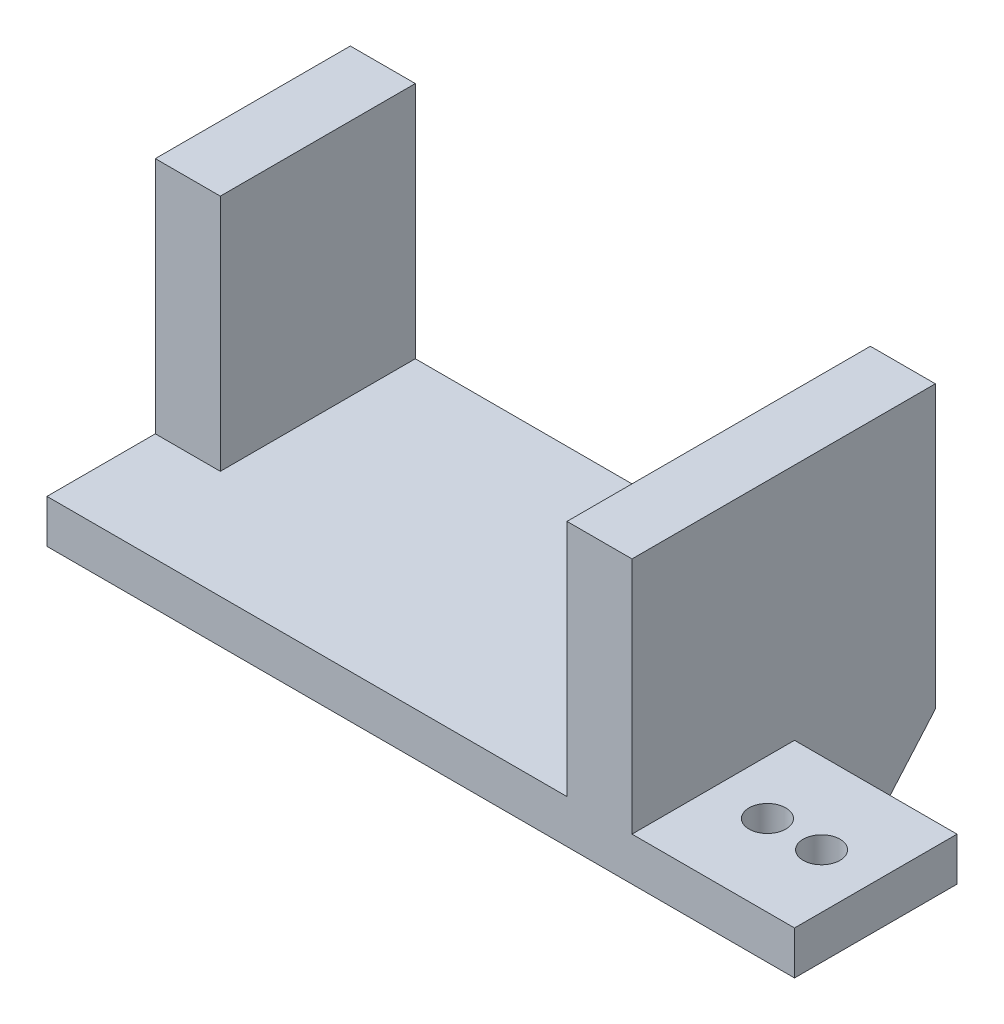
SolidWorks part; units mm, degrees
ref_plane "Front" through (0, 0, 0) normal (0, 0, 1) x (1, 0, 0)
ref_plane "Top" through (0, 0, 0) normal (0, 1, 0) x (1, 0, 0)
ref_plane "Right" through (0, 0, 0) normal (1, 0, 0) x (0, 0, -1)
sketch "Sketch1" plane through (0, 0, 0) normal (0, 0, 1) x (1, 0, 0)
  line L0 (-21, 0) -> (21, 0)
  line L1 (21, 0) -> (21, 26)
  line L2 (21, 26) -> (27, 26)
  line L3 (27, 26) -> (27, 4)
  line L4 (27, 4) -> (42, 4)
  line L5 (42, 4) -> (42, 0)
  line L6 (42, 0) -> (21, 0)
  line L7 (21, 4) -> (-21, 4)
  line L8 (0, 4) -> (0, 0)
  line L9 (-42, 0) -> (-21, 0)
  line L10 (-42, 4) -> (-42, 0)
  line L11 (-27, 4) -> (-42, 4)
  line L12 (-27, 26) -> (-27, 4)
  line L13 (-21, 26) -> (-27, 26)
  line L14 (-21, 0) -> (-21, 26)
  point P4 (0, 0)
  point P19 (24, 26)
  point P20 (-24, 26)
  dimension "D1" = 4
  dimension "D2" = 6
  dimension "D3" = 26
  dimension "D4" = 15
  dimension "D5" = 48
  dimension "D6" = 0
extrude "Boss-Extrude1" add sketch "Sketch1" along normal blind 15 contours L6 L5 L4 L3 L2 L1 | L14 L0 L8 L7 | L7 L8 L0 L1 | L9 L14 L13 L12 L11 L10 region at (-10.5, 2, 0) region at (-26.9167, 9.9444, 0) region at (10.5, 2, 0) region at (26.9167, 9.9444, 0)
sketch "Sketch2" plane through (0, 0, 0) normal (0, 0, -1) x (-1, 0, 0)
  line L0 (-27, 26) -> (-27, 0)
  line L1 (-42, 0) -> (42, 0) construction
  line L2 (-27, 26) -> (-21, 26)
  line L3 (-21, 26) -> (-27, 26) construction
  line L4 (-21, 26) -> (-21, 4)
  line L5 (-21, 4) -> (21, 4)
  line L6 (21, 4) -> (21, 26)
  line L7 (21, 26) -> (27, 26)
  line L8 (27, 26) -> (27, 4)
  line L9 (27, 4) -> (27, 0)
  line L10 (27, 0) -> (-27, 0)
extrude "Boss-Extrude2" add sketch "Sketch2" along normal blind 13
sketch "Sketch3" plane through (0, 0, -13) normal (0, 0, -1) x (-1, 0, 0)
  line L0 (-24, 26) -> (-24, 6)
  line L2 (-21, 26) -> (-27, 26) construction
  line L3 (24, 26) -> (24, 6)
  line L5 (27, 26) -> (21, 26) construction
  line L6 (-24, 20.95) -> (-24, 11.05)
  line L7 (24, 20.95) -> (24, 11.05)
  circle A0 centre (-24, 20.95) radius 1.8
  circle A1 centre (-24, 11.05) radius 1.8
  circle A2 centre (24, 20.95) radius 1.8
  circle A3 centre (24, 11.05) radius 1.8
  point P11 (-24, 16)
  point P14 (24, 16)
  dimension "D1" = 20
  dimension "D2" = 20
  dimension "D3" = 9.9
  dimension "D4" = 9.9
extrude "Cut-Extrude1" cut sketch "Sketch3" against normal blind 10 contours L0 A0 | A0 | A1 | A2 | A3 region at (23.2361, 20.95, -13)
sketch "Sketch4" plane through (0, 4, 0) normal (0, 1, 0) x (1, 0, 0)
  line L0 (-42, 0) -> (-27, 0)
  line L1 (-27, 0) -> (-27, -15)
  line L2 (-27, -15) -> (-42, -15)
  line L3 (-42, -15) -> (-42, 0)
  line L4 (42, -7.5) -> (37, -7.5)
  line L5 (42, -15) -> (42, 0) construction
  line L6 (37, -7.5) -> (32, -7.5)
  circle A0 centre (37, -7.5) radius 1.7
  circle A1 centre (32, -7.5) radius 1.7
  line M3 (-27, 0) -> (-42, 0)
  line M4 (-42, 0) -> (-42, -15)
  line M5 (-42, -15) -> (-27, -15)
  line M6 (-27, -15) -> (-27, 0)
  dimension "D1" = 5
  dimension "D2" = 5
extrude "Cut-Extrude2" cut sketch "Sketch4" against normal blind 15 contours M6 M3 M4 M5 | A0 | A1 region at (-34.5, 4, 7.5)
sketch "Sketch5" plane through (0, 26, 0) normal (0, 1, 0) x (1, 0, 0)
  line L0 (-27, -15) -> (-27, -5)
  line L1 (-27, -15) -> (-27, 13) construction
  line L2 (-27, -5) -> (-21, -5)
  line L3 (-21, -15) -> (-21, 13) construction
  line L4 (-21, -5) -> (-21, -15)
  line L5 (-21, -15) -> (-27, -15)
  dimension "D1" = 10
extrude "Cut-Extrude3" cut sketch "Sketch5" against normal blind 22
sketch "Sketch6" plane through (-27, 0, 0) normal (-1, 0, 0) x (0, 0, 1)
  line L0 (-13, 0) -> (0, 0)
  line L1 (-13, 0) -> (15, 0) construction
  line L2 (0, 0) -> (0, -15)
  line L3 (0, -15) -> (-13, 0)
  line L4 (15, 4) -> (15, 0) construction
  dimension "D1" = 15
  dimension "D2" = 15
extrude "Boss-Extrude3" add sketch "Sketch6" against normal blind 54
sketch "Sketch7" plane through (0, 0, -13) normal (0, 0, -1) x (-1, 0, 0)
  line L0 (-21, 0) -> (-21, -15)
  line L1 (-27, 0) -> (27, 0) construction
  line L2 (-21, -15) -> (-3, -15)
  line L3 (-3, -15) -> (-3, 0)
  line L4 (-3, 0) -> (-21, 0)
  line L5 (3, 0) -> (3, -15)
  line L6 (3, -15) -> (21, -15)
  line L7 (21, -15) -> (21, 0)
  line L8 (21, 0) -> (3, 0)
  line L9 (-27, 0) -> (-27, -15) construction
  line L10 (27, 0) -> (27, -15) construction
  line L11 (-3, -15) -> (3, -15)
  line L12 (-21, 4) -> (21, 4)
  point P14 (0, -15)
  point P19 (0, 4)
  line M11 (-27, 0) -> (27, 0)
  dimension "D1" = 6
  dimension "D2" = 6
  dimension "D3" = 6
  dimension "D4" = 15
  dimension "D5" = 15
  dimension "D6" = 0
extrude "Cut-Extrude4" cut sketch "Sketch7" against normal blind 11 contours L2 L3 L0 M11 | L6 L7 L5 M11 region at (12, -7.5, -13) region at (-12, -7.5, -13)
